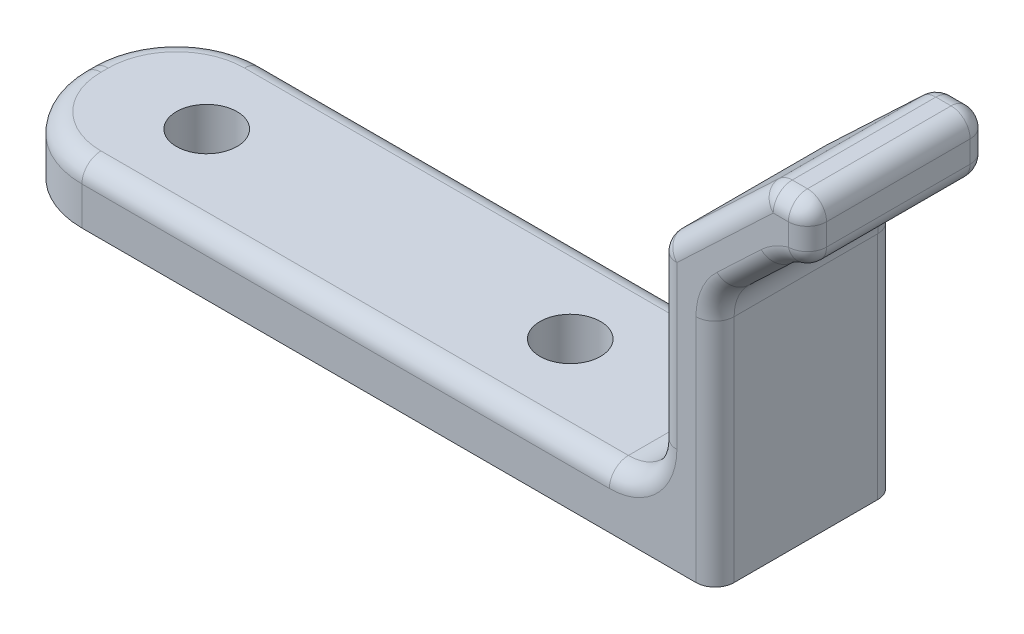
SolidWorks part; units mm, degrees
ref_plane "Front Plane" through (0, 0, 0) normal (0, 0, 1) x (1, 0, 0)
ref_plane "Top Plane" through (0, 0, 0) normal (0, 1, 0) x (1, 0, 0)
ref_plane "Right Plane" through (0, 0, 0) normal (1, 0, 0) x (0, 0, -1)
sketch "Sketch1" plane through (0, 0, 0) normal (0, 1, 0) x (1, 0, 0)
  line L1 (-15.875, -4.7625) -> (15.875, -4.7625)
  line L2 (-15.875, -4.7625) -> (-15.875, 4.7625)
  line L3 (-15.875, 4.7625) -> (15.875, 4.7625)
  line L4 (15.875, -4.7625) -> (15.875, 4.7625)
  line L5 (-15.875, -4.7625) -> (15.875, 4.7625) construction
  line L6 (-15.875, 4.7625) -> (15.875, -4.7625) construction
  point P0 (0, 0)
  dimension "D1" = 9.525
  dimension "D2" = 31.75
extrude "Boss-Extrude1" add sketch "Sketch1" along normal blind 3
sketch "Sketch2" plane through (0, 3, 0) normal (0, 1, 0) x (1, 0, 0)
  line L0 (-9.525, 0) -> (9.525, 0) construction
  circle A0 centre (-9.525, 0) radius 1.5875
  circle A1 centre (9.525, 0) radius 1.5875
  dimension "D2" = 3.175
  dimension "D3" = 3.175
  dimension "D1" = 19.05
extrude "Cut-Extrude1" cut sketch "Sketch2" against normal through all
fillet "Fillet1" radius 4.572 2 edges at (-15.875, 1.5, 4.7625) (-15.875, 1.5, -4.7625)
sketch "Sketch3" plane through (15.875, 0, 0) normal (1, 0, 0) x (0, 0, -1)
  line L1 (-4.7625, 3) -> (4.7625, 3)
  line L2 (-4.7625, 3) -> (-4.7625, 0)
  line L3 (-4.7625, 0) -> (4.7625, 0)
  line L4 (4.7625, 3) -> (4.7625, 0)
extrude "Boss-Extrude2" add sketch "Sketch3" along normal blind 6
sketch "Sketch5" plane through (0, 0, 4.7625) normal (0, 0, 1) x (1, 0, 0)
  line L0 (18.875, 3) -> (18.875, 14.452)
  line L1 (-11.303, 3) -> (21.875, 3) construction
  line L2 (18.875, 14.452) -> (24.5244, 19.7945)
  line L3 (24.5244, 19.7945) -> (26.7182, 19.7945)
  line L4 (26.7182, 19.7945) -> (26.7182, 16.7945)
  line L5 (26.7182, 16.7945) -> (25.7182, 16.7945)
  line L6 (25.7182, 16.7945) -> (21.875, 13.16)
  line L7 (21.875, 13.16) -> (21.875, 3)
  line L8 (21.875, 3) -> (18.875, 3)
  point P4 (21.875, 3)
  point P11 (20.3476, 21.9878)
  point P13 (24.6982, 18.9679)
  point P14 (30.7853, 23.0046)
  point P15 (23.0323, 23.0046)
  point P16 (21.875, 14.5467)
  point P17 (26.6821, 19.8649)
  point P18 (18.875, 14.3545)
  point P19 (32.4513, 24.6847)
  point P20 (18.875, 17.0414)
  point P21 (27.8379, 24.7987)
  point P22 (26.5762, 21.7395)
  point P23 (25.7182, 19.4147)
  dimension "D1" = 3
  dimension "D2" = 3
  dimension "D3" = 3
  dimension "D4" = 1
  dimension "D5" = 10.16
extrude "Boss-Extrude3" add sketch "Sketch5" against normal up to surface (9.525 mm away) up to face at (5.286, 1.5, -4.7625)
fillet "Fillet3" radius 2.54 2 edges at (21.875, 13.16, 0) (25.7182, 16.7945, 0)
fillet "Fillet4" radius 1 4 edges at (18.875, 14.452, 0) (24.5244, 19.7945, 0) (26.7182, 19.7945, 0) (26.7182, 16.7945, 0)
fillet "Fillet5" radius 2.54 1 edges at (18.875, 3, 0)
fillet "Fillet7" radius 1 31 edges at (21.875, 6.0331, -4.7625) (22.0821, 13.0708, -4.7625) (23.8268, 15.0058, -4.7625) (25.4592, 16.4543, -4.7625) (26.52, 17.0494, -4.7625) (26.7182, 18.2208, -4.7625) (26.4253, 19.5016, -4.7625) (25.3203, 19.7945, -4.7625) (24.5526, 19.7236, -4.7625) (21.7116, 17.1345, -4.7625) (18.9566, 14.4169, -4.7625) (18.875, 9.7807, -4.7625) (18.1311, 3.7439, -4.7625) (2.516, 3, -4.7625) (-14.5359, 3, -3.4234) (-15.875, 3, 0) (-14.5359, 3, 3.4234) (21.875, 6.0331, 4.7625) (22.0821, 13.0708, 4.7625) (23.8268, 15.0058, 4.7625) (25.4592, 16.4543, 4.7625) (26.52, 17.0494, 4.7625) (26.7182, 18.2208, 4.7625) (26.4253, 19.5016, 4.7625) (25.3203, 19.7945, 4.7625) (24.5526, 19.7236, 4.7625) (21.7116, 17.1345, 4.7625) (18.9566, 14.4169, 4.7625) (18.875, 9.7807, 4.7625) (18.1311, 3.7439, 4.7625) (2.516, 3, 4.7625)
